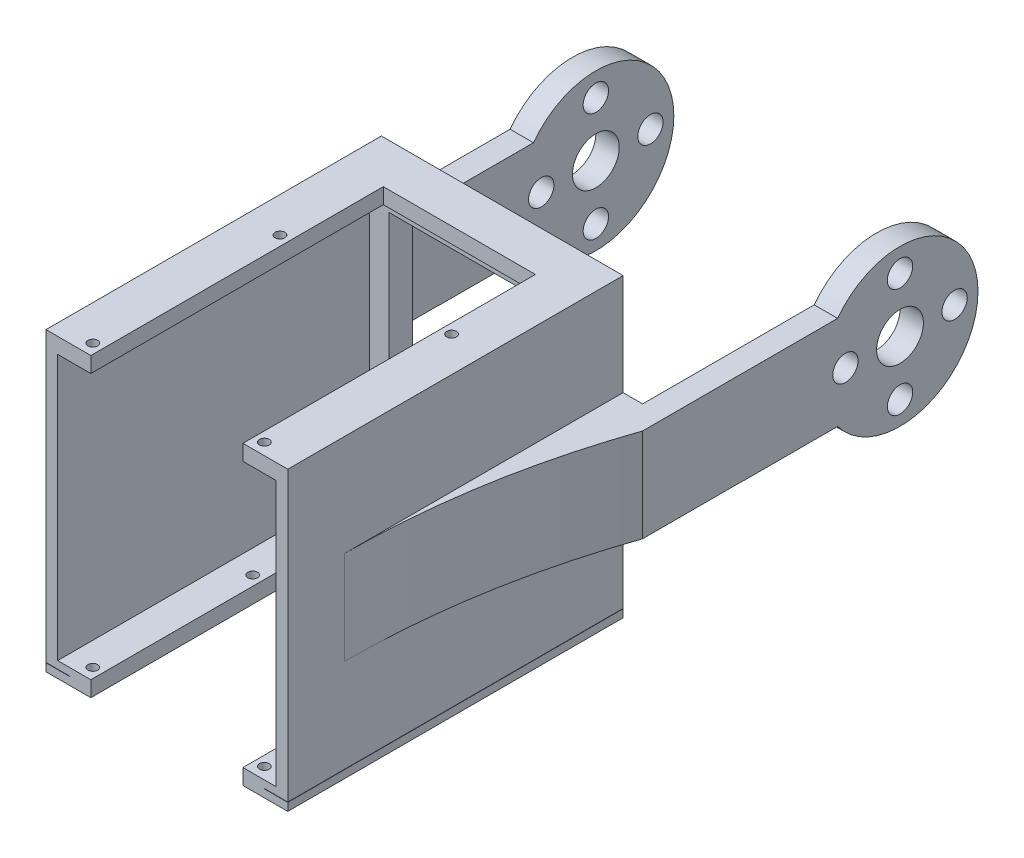
SolidWorks part; units mm, degrees
ref_plane "Front Plane" through (0, 0, 0) normal (0, 0, 1) x (1, 0, 0)
ref_plane "Top Plane" through (0, 0, 0) normal (0, 1, 0) x (1, 0, 0)
ref_plane "Right Plane" through (0, 0, 0) normal (1, 0, 0) x (0, 0, -1)
sketch "Sketch1" plane through (0, 0, 0) normal (0, 0, 1) x (1, 0, 0)
  line L0 (12.5, 12.5) -> (21, 12.5)
  line L1 (-12.5, 18) -> (12.5, 18)
  line L2 (-12.5, 18) -> (-12.5, 12.5)
  line L3 (-12.5, -18) -> (12.5, -18)
  line L4 (12.5, 18) -> (12.5, 12.5)
  line L5 (-12.5, 18) -> (12.5, -18) construction
  line L6 (-12.5, -18) -> (12.5, 18) construction
  line L7 (-21, 12.5) -> (-12.5, 12.5)
  line L8 (-21, 12.5) -> (-21, -12.5)
  line L9 (-21, -12.5) -> (-12.5, -12.5)
  line L10 (21, 12.5) -> (21, -12.5)
  line L11 (-21, 12.5) -> (21, -12.5) construction
  line L12 (-21, -12.5) -> (21, 12.5) construction
  line L13 (-12.5, -12.5) -> (-12.5, -18)
  line L14 (12.5, -12.5) -> (21, -12.5)
  line L15 (12.5, -12.5) -> (12.5, -18)
  point P0 (0, 0)
  point P6 (0, 0)
  dimension "D1" = 25
  dimension "D2" = 36
  dimension "D3" = 25
  dimension "D4" = 42
extrude "Boss-Extrude1" add sketch "Sketch1" along normal blind 3
sketch "Sketch2" plane through (0, 0, 3) normal (0, 0, 1) x (1, 0, 0)
  line L0 (12.5, 12.5) -> (12.5, 18) construction
  line L1 (-12.5, 18) -> (12.5, 18)
  line L2 (-12.5, 18) -> (-12.5, 16)
  line L3 (-12.5, 16) -> (12.5, 16)
  line L4 (12.5, 18) -> (12.5, 16)
  line L5 (-12.5, 18) -> (12.5, 16) construction
  line L6 (-12.5, 16) -> (12.5, 18) construction
  line L7 (12.5, -18) -> (12.5, -12.5) construction
  line L8 (-12.5, -16) -> (12.5, -16)
  line L9 (-12.5, -16) -> (-12.5, -18)
  line L10 (-12.5, -18) -> (12.5, -18)
  line L11 (12.5, -16) -> (12.5, -18)
  line L12 (-12.5, -16) -> (12.5, -18) construction
  line L13 (-12.5, -18) -> (12.5, -16) construction
  line L14 (12.5, 18) -> (-12.5, 18) construction
  point P0 (0, 17)
  point P7 (0, -17)
  dimension "D1" = 2
  dimension "D2" = 2
  dimension "D3" = 0
  dimension "D4" = 0
extrude "Boss-Extrude2" add sketch "Sketch2" along normal blind 40
sketch "Sketch3" plane through (0, 18, 0) normal (0, 1, 0) x (1, 0, 0)
  line L0 (-12.5, -43) -> (-12.5, 0) construction
  line L1 (12.5, -43) -> (12.5, 0) construction
  line L2 (12.5, -43) -> (-12.5, -43) construction
  circle A0 centre (-11, -17.5) radius 0.625
  circle A1 centre (11, -17.5) radius 0.625
  circle A2 centre (-11, -41.5) radius 0.625
  circle A3 centre (11, -41.5) radius 0.625
  dimension "D3" = 1.25
  dimension "D4" = 1.25
  dimension "D6" = 1.25
  dimension "D7" = 1.25
  dimension "D1" = 1.5
  dimension "D2" = 1.5
  dimension "D5" = 24
  dimension "D8" = 1.5
  dimension "D9" = 1.5
  dimension "D10" = 1.5
  dimension "D11" = 1.5
extrude "Cut-Extrude1" cut sketch "Sketch3" against normal blind 3
sketch "Sketch4" plane through (0, -16, 0) normal (0, 1, 0) x (1, 0, 0)
  circle A0 centre (-11, -41.5) radius 0.625
  circle A1 centre (11, -41.5) radius 0.625
  circle A2 centre (-11, -21) radius 0.625
  circle A3 centre (11, -21) radius 0.625
  dimension "D1" = 1.25
  dimension "D2" = 1.25
  dimension "D3" = 20.5
extrude "Cut-Extrude2" cut sketch "Sketch4" against normal blind 3
sketch "Sketch5" plane through (0, 0, 0) normal (0, 0, -1) x (-1, 0, 0)
  line L0 (-12.5, -12.5) -> (-21, -12.5) construction
  line L1 (-21, 12.5) -> (-18, 12.5)
  line L2 (-21, 12.5) -> (-21, -12.5)
  line L3 (-21, -12.5) -> (-18, -12.5)
  line L4 (-18, 12.5) -> (-18, -12.5)
  line L5 (-21, 12.5) -> (-18, -12.5) construction
  line L6 (-21, -12.5) -> (-18, 12.5) construction
  line L7 (12.5, 12.5) -> (21, 12.5) construction
  line L8 (21, -12.5) -> (18, -12.5)
  line L9 (21, -12.5) -> (21, 12.5)
  line L10 (21, 12.5) -> (18, 12.5)
  line L11 (18, -12.5) -> (18, 12.5)
  line L12 (21, -12.5) -> (18, 12.5) construction
  line L13 (21, 12.5) -> (18, -12.5) construction
  point P0 (-19.5, 0)
  point P7 (19.5, 0)
  dimension "D1" = 3
  dimension "D2" = 3
  dimension "D3" = 5.5
  dimension "D4" = 0
extrude "Boss-Extrude3" add sketch "Sketch5" along normal blind 40
sketch "Sketch6" plane through (21, 0, 0) normal (1, 0, 0) x (0, 0, -1)
  line L0 (30, 10) -> (30, 12.5)
  line L1 (-3, 12.5) -> (40, 12.5) construction
  line L2 (30, 12.5) -> (46.4573, 12.5)
  line L3 (46.4573, 12.5) -> (46.4573, -12.5)
  line L4 (46.4573, -12.5) -> (30, -12.5)
  line L5 (-3, -12.5) -> (40, -12.5) construction
  line L6 (30, -12.5) -> (30, -10)
  arc A0 (30, -10) -> (30, 10) centre (30, 0) ccw
  circle A1 centre (30, 7) radius 1.625
  circle A2 centre (30, 0) radius 3
  circle A3 centre (37, 0) radius 1.625
  circle A4 centre (30, -7) radius 1.625
  circle A5 centre (23, 0) radius 1.625
  dimension "D1" = 20
  dimension "D2" = 30
  dimension "D3" = 4
  dimension "D4" = 7
sketch "Sketch7" plane through (0, 18, 0) normal (0, 1, 0) x (1, 0, 0)
  line L0 (12.5, -43) -> (-12.5, -43) construction
  line L1 (-9.75, -80.5) -> (9.75, -80.5)
  line L2 (-9.75, -80.5) -> (-9.75, -5.5)
  line L3 (-9.75, -5.5) -> (9.75, -5.5)
  line L4 (9.75, -80.5) -> (9.75, -5.5)
  line L5 (-9.75, -80.5) -> (9.75, -5.5) construction
  line L6 (-9.75, -5.5) -> (9.75, -80.5) construction
  point P0 (0, -43)
  dimension "D1" = 75
  dimension "D2" = 19.5
extrude "Cut-Extrude5" cut sketch "Sketch7" against normal blind 40
sketch "Sketch10" plane through (0, 18, 0) normal (0, 1, 0) x (1, 0, 0)
  line L1 (-12.5, 0) -> (12.5, 0)
  line L2 (-12.5, 0) -> (-12.5, -3)
  line L3 (-12.5, -3) -> (12.5, -3)
  line L4 (12.5, 0) -> (12.5, -3)
extrude "Boss-Extrude4" add sketch "Sketch10" along normal blind 10
sketch "Sketch11" plane through (0, -18, 0) normal (0, -1, 0) x (1, 0, 0)
  line L0 (12.5, 43) -> (12.5, 0) construction
  line L1 (-12.5, 0) -> (12.5, 0)
  line L2 (-12.5, 0) -> (-12.5, 3)
  line L3 (-12.5, 3) -> (12.5, 3)
  line L4 (12.5, 0) -> (12.5, 3)
extrude "Boss-Extrude5" add sketch "Sketch11" along normal blind 10
sketch "Sketch12" plane through (-21, 0, 0) normal (-1, 0, 0) x (0, 0, 1)
  line L0 (3, -12.5) -> (-40, -12.5) construction
  line L1 (3, 12.5) -> (0, 12.5)
  line L2 (3, 12.5) -> (3, -12.5)
  line L3 (3, -12.5) -> (0, -12.5)
  line L4 (0, 12.5) -> (0, -12.5)
  line L5 (0, -12.5) -> (0, -28) construction
extrude "Boss-Extrude6" add sketch "Sketch12" along normal blind 10
sketch "Sketch13" plane through (21, 0, 0) normal (1, 0, 0) x (0, 0, -1)
  line L0 (-3, -12.5) -> (40, -12.5) construction
  line L1 (-3, 12.5) -> (0, 12.5)
  line L2 (-3, 12.5) -> (-3, -12.5)
  line L3 (-3, -12.5) -> (0, -12.5)
  line L4 (0, 12.5) -> (0, -12.5)
extrude "Boss-Extrude7" add sketch "Sketch13" along normal blind 10
sketch "Sketch14" plane through (-12.5, 0, 0) normal (-1, 0, 0) x (0, 0, 1)
  line L0 (0, -12.5) -> (0, -28) construction
  line L5 (43, 18) -> (0, 18)
  line L6 (43, 18) -> (43, -17.9581)
  line L7 (43, -17.9581) -> (0, -17.9581)
  line L8 (0, 18) -> (0, -17.9581)
extrude "Boss-Extrude11" add sketch "Sketch14" along normal blind 3
sketch "Sketch15" plane through (12.5, 0, 0) normal (1, 0, 0) x (0, 0, -1)
  line L1 (-43, 18) -> (0, 18)
  line L2 (-43, 18) -> (-43, -17.9581)
  line L3 (-43, -17.9581) -> (0, -17.9581)
  line L4 (0, 18) -> (0, -17.9581)
extrude "Boss-Extrude12" add sketch "Sketch15" along normal blind 3
sketch "Sketch16" plane through (0, 0, 0) normal (0, 0, -1) x (-1, 0, 0)
  line L0 (-15.5, 12.5) -> (-15.5, 18) construction
  line L1 (-11.5, 14) -> (11.5, 14)
  line L2 (-11.5, 14) -> (-11.5, -14)
  line L3 (-11.5, -14) -> (11.5, -14)
  line L4 (11.5, 14) -> (11.5, -14)
  line L5 (-11.5, 14) -> (11.5, -14) construction
  line L6 (-11.5, -14) -> (11.5, 14) construction
  line L7 (15.5, 18) -> (12.5, 18) construction
  point P0 (0, 0)
  dimension "D1" = 4
  dimension "D2" = 4
extrude "Cut-Extrude6" cut sketch "Sketch16" against normal blind 13
extrude "Cut-Extrude7" cut sketch "Sketch6" against normal through all both and the other way through all
fillet "Fillet1" radius 10 1 edges at (31, 12.5, 1.5)
fillet "Fillet2" radius 10 7 edges at (12.5, 28, 1.5) (-12.5, 28, 1.5) (-31, 12.5, 1.5) (12.5, -28, 1.5) (-31, -12.5, 1.5) (-12.5, -28, 1.5) (31, -12.5, 1.5)
sketch "Sketch17" plane through (0, 0, -30) normal (0, 0, -1) x (-1, 0, 0)
  line L1 (-21, 12.5) -> (-18, 12.5)
  line L2 (-21, 12.5) -> (-21, 10)
  line L3 (-21, 10) -> (-18, 10)
  line L4 (-18, 12.5) -> (-18, 10)
  line L5 (-21, -12.5) -> (-18, -12.5)
  line L6 (-21, -12.5) -> (-21, -10)
  line L7 (-21, -10) -> (-18, -10)
  line L8 (-18, -12.5) -> (-18, -10)
  line L9 (18, 12.5) -> (21, 12.5)
  line L10 (18, 12.5) -> (18, 10)
  line L11 (18, 10) -> (21, 10)
  line L12 (21, 12.5) -> (21, 10)
  line L13 (18, -10) -> (21, -10)
  line L14 (18, -10) -> (18, -12.5)
  line L15 (18, -12.5) -> (21, -12.5)
  line L16 (21, -10) -> (21, -12.5)
extrude "Cut-Extrude8" cut sketch "Sketch17" against normal blind 30
sketch "Sketch19" plane through (0, 0, 43) normal (0, 0, 1) x (1, 0, 0)
  line L1 (-14, 16) -> (14, 16)
  line L2 (-14, 16) -> (-14, -16)
  line L3 (-14, -16) -> (14, -16)
  line L4 (14, 16) -> (14, -16)
  line L5 (-14, 16) -> (14, -16) construction
  line L6 (-14, -16) -> (14, 16) construction
  point P0 (0, 0)
  dimension "D1" = 28
extrude "Cut-Extrude9" cut sketch "Sketch19" against normal blind 40
sketch "Sketch20" plane through (0, 0, 3) normal (0, 0, 1) x (1, 0, 0)
  line L0 (-9.75, 18) -> (-15.5, 18) construction
  line L5 (-12.625, 18) -> (12.625, 18)
  line L6 (-12.625, 18) -> (-12.625, 29.8476)
  line L7 (-12.625, 29.8476) -> (12.625, 29.8476)
  line L8 (12.625, 18) -> (12.625, 29.8476)
  line L14 (-12.5, -18) -> (12.5, -18)
  line L15 (-12.5, -18) -> (-12.5, -31.8375)
  line L16 (-12.5, -31.8375) -> (12.5, -31.8375)
  line L17 (12.5, -18) -> (12.5, -31.8375)
extrude "Cut-Extrude11" cut sketch "Sketch20" against normal through all both and the other way through all
sketch "Sketch21" plane through (-21, 0, 0) normal (-1, 0, 0) x (0, 0, 1)
  line L0 (-30, 10) -> (0, 10)
  line L1 (0, 10) -> (0, 6)
  line L2 (0, -10) -> (0, 10) construction
  line L3 (0, 6) -> (-22, 6)
  line L4 (-22, -6) -> (0, -6)
  line L5 (0, -6) -> (0, -10)
  line L6 (0, -10) -> (-30, -10)
  arc A0 (-30, -10) -> (-22, -6) centre (-30, 0) ccw
  arc A1 (-22, 6) -> (-30, 10) centre (-30, 0) ccw
  dimension "D1" = 4
  dimension "D2" = 4
extrude "Cut-Extrude12" cut sketch "Sketch21" against normal through all both and the other way through all
sketch "Sketch22" plane through (0, 0, 0) normal (0, 0, -1) x (-1, 0, 0)
  line L1 (21, 12.5) -> (31, 12.5)
  line L2 (21, 12.5) -> (21, -12.5)
  line L3 (21, -12.5) -> (31, -12.5)
  line L4 (31, 12.5) -> (31, -12.5)
  line L5 (-21, 12.5) -> (-31, 12.5)
  line L6 (-21, 12.5) -> (-21, -12.5)
  line L7 (-21, -12.5) -> (-31, -12.5)
  line L8 (-31, 12.5) -> (-31, -12.5)
extrude "Cut-Extrude13" cut sketch "Sketch22" against normal through all both and the other way through all
sketch "Sketch24" plane through (0, 0, 0) normal (0, 0, -1) x (-1, 0, 0)
  line L1 (21, 12.5) -> (15.5, 12.5)
  line L2 (21, 12.5) -> (21, 6)
  line L3 (21, 6) -> (15.5, 6)
  line L4 (15.5, 12.5) -> (15.5, 6)
  line L5 (21, -12.5) -> (15.5, -12.5)
  line L6 (21, -12.5) -> (21, -5.9747)
  line L7 (21, -5.9747) -> (15.5, -5.9747)
  line L8 (15.5, -12.5) -> (15.5, -5.9747)
  line L9 (-21, -12.5) -> (-15.5, -12.5)
  line L10 (-21, -12.5) -> (-21, -5.9747)
  line L11 (-21, -5.9747) -> (-15.5, -5.9747)
  line L12 (-15.5, -12.5) -> (-15.5, -5.9747)
  line L13 (-21, 12.5) -> (-15.5, 12.5)
  line L14 (-21, 12.5) -> (-21, 6)
  line L15 (-21, 6) -> (-15.5, 6)
  line L16 (-15.5, 12.5) -> (-15.5, 6)
extrude "Cut-Extrude14" cut sketch "Sketch24" against normal blind 10 and the other way blind 10
fillet "Fillet3" radius 100 1 edges at (-15.5, 0.0127, 3) first distance on face at (-15.5, 0.0168, 11.5)
fillet "Fillet4" radius 100 1 edges at (15.5, 0.0127, 3) first distance on face at (18.25, 0.0127, 3)
sketch "Sketch25" plane through (0, 0, 43) normal (0, 0, 1) x (1, 0, 0)
  line L6 (-14, 16) -> (14, 16) construction
  line L7 (-14, 17) -> (14, 17)
  line L13 (-14, 17) -> (-14, 15)
  line L14 (-14, 15) -> (14, 15)
  line L15 (14, 17) -> (14, 15)
  line L16 (-14, 17) -> (14, 15) construction
  line L17 (-14, 15) -> (14, 17) construction
  line L18 (14, -16) -> (14, 16) construction
  line L19 (14, -16) -> (-14, -16) construction
  line L20 (-14, -15) -> (14, -15)
  line L21 (-14, -15) -> (-14, -17)
  line L22 (-14, -17) -> (14, -17)
  line L23 (14, -15) -> (14, -17)
  line L24 (-14, -15) -> (14, -17) construction
  line L25 (-14, -17) -> (14, -15) construction
  point P0 (0, 16)
  point P9 (0, -16)
  dimension "D1" = 1
  dimension "D2" = 2
extrude "Cut-Extrude17" cut sketch "Sketch25" against normal blind 40
sketch "Sketch26" plane through (0, 18, 0) normal (0, 1, 0) x (1, 0, 0)
  line L0 (-15.5, -43) -> (-15.5, 0)
  line L1 (-15.5, 0) -> (15.5, 0)
  line L2 (15.5, 0) -> (15.5, -43)
  line L3 (15.5, -43) -> (9.75, -43)
  line L4 (9.75, -43) -> (9.75, -5.5)
  line L5 (9.75, -5.5) -> (-9.75, -5.5)
  line L6 (-9.75, -5.5) -> (-9.75, -43)
  line L7 (-9.75, -43) -> (-15.5, -43)
  circle A0 centre (-11, -41.5) radius 0.625
  circle A1 centre (-11, -17.5) radius 0.625
  circle A2 centre (11, -17.5) radius 0.625
  circle A3 centre (11, -41.5) radius 0.625
extrude "Boss-Extrude13" add sketch "Sketch26" along normal blind 1
sketch "Sketch27" plane through (0, -18, 0) normal (0, -1, 0) x (1, 0, 0)
  line L0 (-15.5, 43) -> (-9.75, 43)
  line L1 (-9.75, 43) -> (-9.75, 5.5)
  line L2 (9.75, 5.5) -> (-9.75, 5.5) construction
  line L3 (-9.75, 5.5) -> (-9.75, 43) construction
  line L4 (-9.75, 5.5) -> (9.75, 5.5)
  line L5 (9.75, 5.5) -> (9.75, 43)
  line L6 (9.75, 43) -> (15.5, 43)
  line L7 (15.5, 43) -> (15.5, 0)
  line L8 (15.5, 0) -> (-15.5, 0)
  line L9 (-15.5, 0) -> (-15.5, 43)
  circle A0 centre (-11, 41.5) radius 0.625
  circle A1 centre (-11, 21) radius 0.625
  circle A2 centre (11, 21) radius 0.625
  circle A3 centre (11, 41.5) radius 0.625
extrude "Boss-Extrude14" add sketch "Sketch27" along normal blind 1
